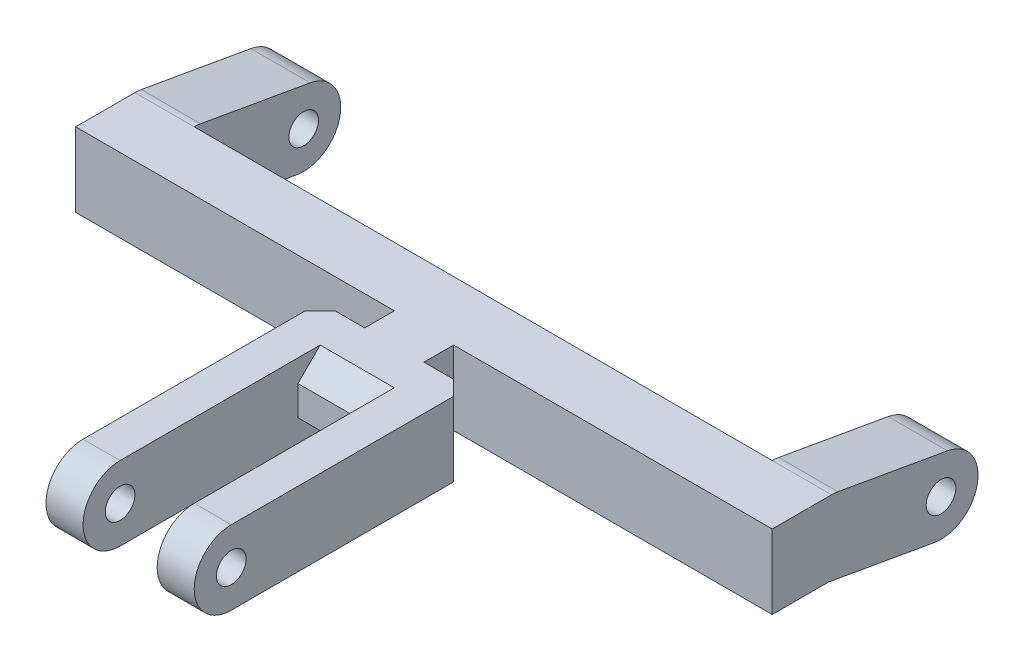
SolidWorks part; units mm, degrees
material "1060 合金"
ref_plane "前视基准面" through (0, 0, 0) normal (0, 0, 1) x (1, 0, 0)
ref_plane "上视基准面" through (0, 0, 0) normal (0, 1, 0) x (1, 0, 0)
ref_plane "右视基准面" through (0, 0, 0) normal (1, 0, 0) x (0, 0, -1)
sketch "草图1" plane through (0, 0, 0) normal (0, 1, 0) x (1, 0, 0)
  line L0 (0, 73.9355) -> (0, -76) construction
  line L9 (-47, 0) -> (47, 0)
  line L23 (47, -8) -> (4, -8)
  line L29 (-10, -20) -> (-10, -12)
  line L32 (10, -20) -> (10, -12)
  line L41 (-10, -12) -> (-4, -12)
  line L42 (10, -20) -> (-10, -20)
  line L43 (-4, -12) -> (-4, -8)
  line L44 (4, -12) -> (4, -8)
  line L45 (4, -12) -> (10, -12)
  line L46 (-4, -8) -> (-47, -8)
  line L47 (-47, -8) -> (-47, 0)
  line L48 (47, -8) -> (47, 0)
  point P19 (0, -19)
  point P20 (0, 19)
  point P21 (0, 0)
  point P23 (0, 2)
  point P24 (0, 0)
  point P27 (0, -15)
  point P28 (0, -70)
  point P30 (0, -7)
  dimension "D1" = 8
  dimension "D2" = 94
  dimension "D3" = 20
  dimension "D4" = 8
  dimension "D5" = 4
  dimension "D11" = 8
extrude "凸台-拉伸1" add sketch "草图1" along normal blind 10
sketch "草图6" plane through (0, 0, 0) normal (1, 0, 0) x (0, 0, -1)
  line L0 (0, 10) -> (0, 0) construction
  line L1 (0.8682, 9.924) -> (15.6404, 7.3193)
  line L2 (-0.8682, 0.076) -> (13.9039, -2.5288)
  line L3 (-8, 10) -> (0, 10) construction
  line L4 (-8, 0) -> (0, 0) construction
  arc A0 (0.8682, 9.924) -> (-0.8682, 0.076) centre (0, 5) ccw
  arc A1 (13.9039, -2.5288) -> (15.6404, 7.3193) centre (14.7721, 2.3953) ccw
  circle A2 centre (14.7721, 2.3953) radius 2
  dimension "D3" = 4
  dimension "D1" = 10
  dimension "D2" = 15
extrude "凸台-拉伸2" add sketch "草图6" against normal blind 8 from surface starting at face at (47, 5, 4)
extrude "凸台-拉伸3" add sketch "草图6<2>" along normal blind 8 from surface starting at face at (-47, 5, 4)
sketch "草图6<2>" plane through (0, 0, 0) normal (1, 0, 0) x (0, 0, -1) same geometry as "草图6"
chamfer "倒角2" distance 2 angle 45 2 edges at (-10, 5, 12) (10, 5, 12)
sketch "草图7" plane through (-10, 0, 0) normal (-1, 0, 0) x (0, 0, 1)
  line L0 (20, 10) -> (20, 0) construction
  line L1 (20, 10) -> (44, 10)
  line L2 (20, 0) -> (44, 0)
  line L3 (14, 0) -> (20, 0) construction
  arc A0 (20, 10) -> (20, 0) centre (20, 5) ccw
  arc A1 (44, 0) -> (44, 10) centre (44, 5) ccw
  circle A2 centre (44, 5) radius 2
  dimension "D3" = 4
  dimension "D1" = 0
  dimension "D2" = 24
extrude "凸台-拉伸4" add sketch "草图7" against normal blind 5
mirror "镜向1" about plane through (0, 0, 0) normal (1, 0, 0) of "凸台-拉伸4"
chamfer "倒角3" distance 3 angle 45 2 edges at (0, 10, 20) (0, 0, 20)
